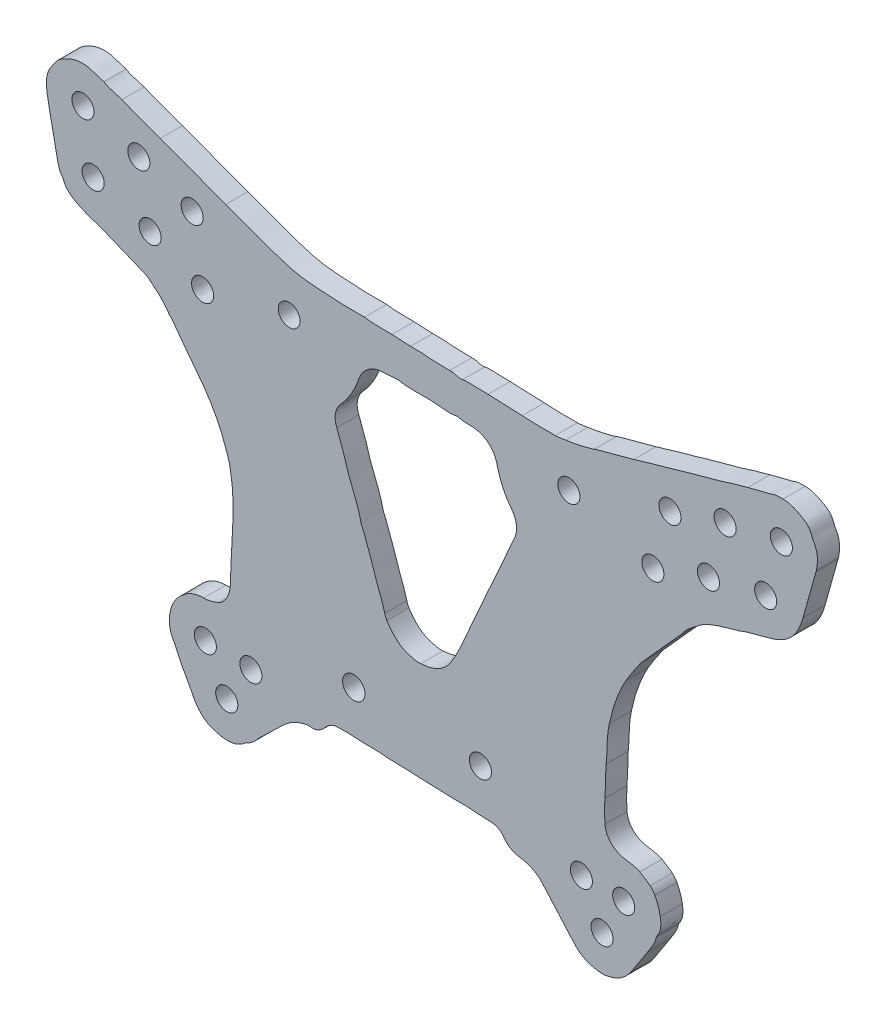
SolidWorks part; units mm, degrees
ref_plane "Front Plane" through (0, 0, 0) normal (0, 0, 1) x (1, 0, 0)
ref_plane "Top Plane" through (0, 0, 0) normal (0, 1, 0) x (1, 0, 0)
ref_plane "Right Plane" through (0, 0, 0) normal (1, 0, 0) x (0, 0, -1)
sketch "Model" plane through (0, 0, 0) normal (0, 0, 1) x (1, 0, 0)
  line L0 (141.9214, 208.6021) -> (124.7332, 209.2379) construction
  line L1 (153.9282, 246.9977) -> (115.9639, 248.6443) construction
  circle A3 centre (153.9282, 246.9977) radius 1.5
  circle A4 centre (167.6388, 251.3937) radius 1.5
  circle A5 centre (165.325, 243.566) radius 1.5
  circle A6 centre (172.8733, 246.2787) radius 1.5
  circle A7 centre (180.6355, 248.0122) radius 1.5
  circle A8 centre (175.1284, 253.7914) radius 1.5
  circle A9 centre (182.7633, 255.3651) radius 1.5
  circle A10 centre (115.9639, 248.6443) radius 1.4757
  circle A11 centre (104.2162, 245.7626) radius 1.5
  circle A12 centre (102.7959, 254.2296) radius 1.5
  circle A13 centre (95.5565, 257.0068) radius 1.5
  circle A14 centre (97.0882, 249.0091) radius 1.5
  circle A15 centre (89.3631, 251.5295) radius 1.5
  circle A16 centre (87.9744, 259.2361) radius 1.5
  circle A17 centre (141.9214, 208.6021) radius 1.5
  circle A18 centre (124.7332, 209.2379) radius 1.5237
  circle A19 centre (110.7635, 204.3383) radius 1.5
  circle A20 centre (104.5864, 204.6703) radius 1.5
  circle A21 centre (107.4953, 199.2811) radius 1.5
  circle A22 centre (155.6235, 202.6037) radius 1.5
  circle A23 centre (161.3646, 202.416) radius 1.5
  circle A24 centre (158.4323, 197.2731) radius 1.5
  spline S0 degree 2 poles (175.3982, 255.0608) (177.2596, 254.4256) (176.3428, 253.0275) knots 0 0 0 1 1 1 construction
  spline S4 degree 3 poles (104.3584, 209.5729) (103.3963, 209.582) (102.5056, 209.2728) (101.7567, 208.6986) (100.4581, 207.7028) (99.7207, 206.3826) (99.7288, 204.7593) knots 139 139 139 139 140 140 140 141 141 141 141
  spline S5 degree 3 poles (106.4003, 210.0532) (105.7457, 209.7831) (105.0841, 209.5661) (104.3584, 209.5729) knots 138 138 138 138 139 139 139 139
  spline S6 degree 3 poles (108.084, 215.6595) (108.0453, 214.815) (108.0317, 213.9694) (108.0027, 213.1244) (107.972, 212.2289) (107.7352, 211.4052) (107.177, 210.6833) (106.9637, 210.4076) (106.7223, 210.186) (106.4003, 210.0532) knots 135 135 135 135 136 136 136 137 137 137 138 138 138 138
  spline S7 degree 3 poles (108.3315, 220.639) (108.2494, 218.9791) (108.1599, 217.3196) (108.084, 215.6595) knots 134 134 134 134 135 135 135 135
  spline S8 degree 3 poles (107.9314, 226.7841) (108.3231, 224.7521) (108.4336, 222.7026) (108.3315, 220.639) knots 133 133 133 133 134 134 134 134
  spline S9 degree 3 poles (107.2797, 228.8777) (107.5183, 228.1848) (107.7919, 227.5075) (107.9314, 226.7841) knots 132 132 132 132 133 133 133 133
  spline S10 degree 3 poles (104.3046, 234.5489) (105.575, 232.807) (106.5754, 230.9228) (107.2797, 228.8777) knots 131 131 131 131 132 132 132 132
  spline S11 degree 3 poles (102.0993, 237.4386) (102.8322, 236.4737) (103.5908, 235.5276) (104.3046, 234.5489) knots 130 130 130 130 131 131 131 131
  spline S12 degree 3 poles (100.177, 240.0096) (100.3186, 239.8346) (100.446, 239.6481) (100.5808, 239.4677) (101.0864, 238.7909) (101.5883, 238.1113) (102.0993, 237.4386) knots 128 128 128 128 129 129 129 130 130 130 130
  spline S13 degree 3 poles (99.4768, 240.8565) (99.6788, 240.5533) (99.9465, 240.2945) (100.177, 240.0096) knots 127 127 127 127 128 128 128 128
  spline S14 degree 3 poles (97.03, 243.2866) (97.9346, 242.5667) (98.825, 241.8346) (99.4768, 240.8565) knots 126 126 126 126 127 127 127 127
  spline S15 degree 3 poles (96.5425, 243.6167) (96.7198, 243.5405) (96.8765, 243.4088) (97.03, 243.2866) knots 125 125 125 125 126 126 126 126
  spline S16 degree 3 poles (94.2001, 244.5874) (94.9821, 244.2667) (95.7662, 243.9506) (96.5425, 243.6167) knots 124 124 124 124 125 125 125 125
  spline S17 degree 3 poles (91.1522, 245.8331) (92.1691, 245.4201) (93.1847, 245.0039) (94.2001, 244.5874) knots 123 123 123 123 124 124 124 124
  spline S18 degree 3 poles (84.2521, 262.4934) (84.0935, 262.2961) (83.9675, 262.0728) (83.8128, 261.872) (83.2374, 261.1251) (82.9868, 260.2683) (83.0191, 259.3425) (83.0395, 258.7547) (83.117, 258.1632) (83.2293, 257.5851) (83.6537, 255.4004) (84.0984, 253.2196) (84.5458, 251.0395) (84.6532, 250.5163) (84.7614, 249.9879) (85.1442, 249.5693) (85.2359, 249.469) (85.2988, 249.3318) (85.3433, 249.2008) (85.6044, 248.4314) (86.1657, 247.9577) (86.8458, 247.5583) (87.9766, 246.8944) (89.2204, 246.5271) (90.4422, 246.097) (90.6803, 246.0132) (90.9184, 245.9281) (91.1522, 245.8331) knots 114 114 114 114 115 115 115 116 116 116 117 117 117 118 118 118 119 119 119 120 120 120 121 121 121 122 122 122 123 123 123 123
  spline S19 degree 3 poles (84.7684, 263.0465) (84.5676, 262.9012) (84.4101, 262.6898) (84.2521, 262.4934) knots 113 113 113 113 114 114 114 114
  spline S20 degree 3 poles (90.819, 263.4802) (90.7301, 263.5394) (90.6019, 263.5372) (90.4949, 263.5724) (90.2007, 263.6693) (89.9044, 263.7612) (89.6155, 263.8723) (87.8351, 264.5569) (86.245, 264.1151) (84.7684, 263.0465) knots 110 110 110 110 111 111 111 112 112 112 113 113 113 113
  spline S21 degree 3 poles (93.2681, 262.593) (92.4577, 262.9035) (91.5642, 262.984) (90.819, 263.4802) knots 109 109 109 109 110 110 110 110
  spline S22 degree 3 poles (98.4862, 260.6456) (97.5614, 260.9799) (96.627, 261.2879) (95.7055, 261.6309) (94.8871, 261.9355) (94.0837, 262.2804) (93.2681, 262.593) knots 107 107 107 107 108 108 108 109 109 109 109
  spline S23 degree 3 poles (107.3488, 257.3186) (105.1052, 258.1548) (102.8653, 259.0007) (100.624, 259.843) (99.9115, 260.1107) (99.202, 260.3869) (98.4862, 260.6456) knots 105 105 105 105 106 106 106 107 107 107 107
  spline S24 degree 3 poles (126.1998, 253.4861) (126.1173, 253.4998) (126.0308, 253.4892) (125.9462, 253.4896) (125.0168, 253.4943) (124.083, 253.4434) (123.1588, 253.5156) (121.5032, 253.6448) (119.8421, 253.6493) (118.1877, 253.8432) (116.4012, 254.0525) (114.7392, 254.6641) (113.0575, 255.2195) (111.9619, 255.5814) (110.8976, 256.0371) (109.8145, 256.4382) (108.9962, 256.7413) (108.1665, 257.0138) (107.3488, 257.3186) knots 99 99 99 99 100 100 100 101 101 101 102 102 102 103 103 103 104 104 104 105 105 105 105
  spline S25 degree 3 poles (129.9103, 253.3202) (128.673, 253.3654) (127.4302, 253.2827) (126.1998, 253.4861) knots 98 98 98 98 99 99 99 99
  spline S26 degree 3 poles (132.4427, 253.1963) (131.5983, 253.2317) (130.7548, 253.2894) (129.9103, 253.3202) knots 97 97 97 97 98 98 98 98
  spline S27 degree 3 poles (137.7603, 253.0066) (136.5498, 253.0258) (135.3367, 252.9843) (134.1333, 253.1683) (134.023, 253.1851) (133.908, 253.1716) (133.7952, 253.1733) (133.3443, 253.18) (132.893, 253.1774) (132.4427, 253.1963) knots 94 94 94 94 95 95 95 96 96 96 97 97 97 97
  spline S28 degree 3 poles (139.4981, 252.8026) (138.887, 252.659) (138.407, 253.0698) (137.8448, 253.0039) (137.8171, 253.0006) (137.7885, 253.0062) (137.7603, 253.0066) knots 92 92 92 92 93 93 93 94 94 94 94
  spline S29 degree 3 poles (142.9535, 252.807) (142.39, 252.8266) (141.8259, 252.8341) (141.2621, 252.8375) (140.672, 252.841) (140.058, 252.9341) (139.4981, 252.8026) knots 90 90 90 90 91 91 91 92 92 92 92
  spline S30 degree 3 poles (147.599, 252.6217) (146.0544, 252.7367) (144.5024, 252.7533) (142.9535, 252.807) knots 89 89 89 89 90 90 90 90
  spline S31 degree 3 poles (152.0761, 252.5182) (150.5831, 252.5305) (149.0922, 252.5105) (147.599, 252.6217) knots 88 88 88 88 89 89 89 89
  spline S32 degree 3 poles (153.4966, 252.6928) (153.0236, 252.6302) (152.5632, 252.5142) (152.0761, 252.5182) knots 87 87 87 87 88 88 88 88
  spline S33 degree 3 poles (157.3671, 253.555) (157.0445, 253.4564) (156.7226, 253.3546) (156.3966, 253.2684) (155.4422, 253.016) (154.4765, 252.8224) (153.4966, 252.6928) knots 85 85 85 85 86 86 86 87 87 87 87
  spline S34 degree 3 poles (162.7378, 255.0407) (161.0561, 254.5745) (159.3688, 254.1282) (157.6845, 253.6714) (157.5762, 253.642) (157.4747, 253.5879) (157.3671, 253.555) knots 83 83 83 83 84 84 84 85 85 85 85
  spline S35 degree 3 poles (178.2268, 259.4881) (177.4648, 259.2872) (176.689, 259.116) (175.9552, 258.8373) (175.3478, 258.6067) (174.732, 258.4454) (174.1068, 258.2847) (172.6885, 257.9201) (171.2828, 257.5071) (169.8723, 257.1125) (169.7638, 257.0821) (169.6592, 257.0384) (169.5511, 257.0068) (169.201, 256.9047) (168.8505, 256.8043) (168.4995, 256.7052) (167.4959, 256.422) (166.4904, 256.1452) (165.4887, 255.8555) (164.57, 255.5898) (163.6592, 255.2961) (162.7378, 255.0407) knots 76 76 76 76 77 77 77 78 78 78 79 79 79 80 80 80 81 81 81 82 82 82 83 83 83 83
  spline S36 degree 3 poles (182.9914, 260.519) (182.4781, 260.5212) (181.9804, 260.5454) (181.4991, 260.3351) (181.3713, 260.2792) (181.2308, 260.2504) (181.0945, 260.2158) (180.1386, 259.9731) (179.1804, 259.7394) (178.2268, 259.4881) knots 73 73 73 73 74 74 74 75 75 75 76 76 76 76
  spline S37 degree 3 poles (187.5208, 254.4157) (187.7469, 255.5503) (187.7604, 256.6541) (187.0898, 257.6746) (186.9685, 257.859) (186.9111, 258.0863) (186.8299, 258.296) (186.6293, 258.8143) (186.2912, 259.2268) (185.8204, 259.5104) (184.9484, 260.0358) (184.0645, 260.5143) (182.9914, 260.519) knots 69 69 69 69 70 70 70 71 71 71 72 72 72 73 73 73 73
  spline S38 degree 3 poles (187.4532, 254.1712) (187.476, 254.2526) (187.5043, 254.333) (187.5208, 254.4157) knots 68 68 68 68 69 69 69 69
  spline S39 degree 3 poles (185.698, 247.9046) (186.2922, 249.9909) (186.8691, 252.0821) (187.4532, 254.1712) knots 67 67 67 67 68 68 68 68
  spline S40 degree 3 poles (184.2825, 245.0495) (185.0094, 245.8818) (185.4031, 246.8688) (185.698, 247.9046) knots 66 66 66 66 67 67 67 67
  spline S41 degree 3 poles (178.0845, 242.424) (178.2136, 242.4767) (178.3578, 242.4913) (178.4937, 242.5286) (179.5521, 242.8192) (180.6132, 243.1006) (181.6667, 243.4081) (182.0167, 243.5103) (182.3561, 243.6615) (182.6841, 243.8233) (183.2958, 244.125) (183.8271, 244.5281) (184.2825, 245.0495) knots 62 62 62 62 63 63 63 64 64 64 65 65 65 66 66 66 66
  spline S42 degree 3 poles (174.3741, 241.2687) (175.6031, 241.6751) (176.8802, 241.9323) (178.0845, 242.424) knots 61 61 61 61 62 62 62 62
  spline S43 degree 3 poles (169.2822, 237.8227) (169.8117, 238.6126) (170.5471, 239.1759) (171.3015, 239.7226) (171.3472, 239.7557) (171.3947, 239.7868) (171.4372, 239.8237) (172.2894, 240.5617) (173.3359, 240.9255) (174.3741, 241.2687) knots 58 58 58 58 59 59 59 60 60 60 61 61 61 61
  spline S44 degree 3 poles (168.7158, 237.1957) (168.9032, 237.4064) (169.127, 237.5912) (169.2822, 237.8227) knots 57 57 57 57 58 58 58 58
  spline S45 degree 3 poles (164.0912, 232.0456) (165.148, 233.214) (166.2063, 234.381) (167.2602, 235.552) (167.7498, 236.096) (168.2294, 236.6488) (168.7158, 237.1957) knots 55 55 55 55 56 56 56 57 57 57 57
  spline S46 degree 3 poles (163.6955, 231.6072) (163.8044, 231.7688) (163.959, 231.8995) (164.0912, 232.0456) knots 54 54 54 54 55 55 55 55
  spline S47 degree 3 poles (161.6936, 228.5732) (162.2927, 229.6235) (163.0184, 230.602) (163.6955, 231.6072) knots 53 53 53 53 54 54 54 54
  spline S48 degree 3 poles (159.4171, 222.3231) (159.8733, 224.5233) (160.5825, 226.6253) (161.6936, 228.5732) knots 52 52 52 52 53 53 53 53
  spline S49 degree 3 poles (158.9825, 217.3704) (159.0092, 217.848) (159.0932, 218.325) (159.0858, 218.8013) (159.0675, 219.9893) (159.1745, 221.1529) (159.4171, 222.3231) knots 50 50 50 50 51 51 51 52 52 52 52
  spline S50 degree 3 poles (158.8105, 213.2372) (158.8669, 214.0246) (158.9261, 214.8069) (158.915, 215.5973) (158.9067, 216.1879) (158.9493, 216.7798) (158.9825, 217.3704) knots 48 48 48 48 49 49 49 50 50 50 50
  spline S51 degree 3 poles (158.822, 210.1979) (158.7394, 211.2055) (158.7382, 212.2288) (158.8105, 213.2372) knots 47 47 47 47 48 48 48 48
  spline S52 degree 3 poles (163.5571, 206.9674) (163.2677, 207.1281) (162.9268, 207.2091) (162.5995, 207.2856) (162.1891, 207.3816) (161.7682, 207.4323) (161.3531, 207.5093) (160.0014, 207.76) (158.9337, 208.836) (158.822, 210.1979) knots 44 44 44 44 45 45 45 46 46 46 47 47 47 47
  spline S53 degree 3 poles (164.9656, 206.0364) (164.526, 206.3854) (164.0483, 206.6945) (163.5571, 206.9674) knots 43 43 43 43 44 44 44 44
  spline S54 degree 3 poles (165.594, 205.255) (165.4379, 205.5461) (165.222, 205.8328) (164.9656, 206.0364) knots 42 42 42 42 43 43 43 43
  spline S55 degree 3 poles (166.3271, 203.102) (166.2036, 203.8558) (165.9553, 204.5815) (165.594, 205.255) knots 41 41 41 41 42 42 42 42
  spline S56 degree 3 poles (165.9276, 200.6658) (166.4643, 201.4128) (166.466, 202.2539) (166.3271, 203.102) knots 40 40 40 40 41 41 41 41
  spline S57 degree 3 poles (165.7841, 200.361) (165.8105, 200.4682) (165.863, 200.5758) (165.9276, 200.6658) knots 39 39 39 39 40 40 40 40
  spline S58 degree 3 poles (164.5379, 197.9739) (165.0235, 198.7329) (165.5632, 199.4631) (165.7841, 200.361) knots 38 38 38 38 39 39 39 39
  spline S59 degree 3 poles (162.3802, 194.6382) (162.7451, 195.1737) (163.0918, 195.7216) (163.4434, 196.2659) (163.8104, 196.8339) (164.1735, 197.4043) (164.5379, 197.9739) knots 36 36 36 36 37 37 37 38 38 38 38
  spline S60 degree 3 poles (158.9744, 192.4901) (160.4094, 192.7321) (161.5577, 193.4311) (162.3802, 194.6382) knots 35 35 35 35 36 36 36 36
  spline S61 degree 3 poles (150.3394, 199.0158) (151.5484, 197.639) (152.7682, 196.2716) (153.9733, 194.8915) (154.4743, 194.3176) (154.9591, 193.7342) (155.5909, 193.2901) (156.39, 192.7284) (158.0266, 192.3302) (158.9744, 192.4901) knots 32 32 32 32 33 33 33 34 34 34 35 35 35 35
  spline S62 degree 3 poles (146.2557, 200.8356) (146.6427, 200.6324) (147.0574, 200.584) (147.4733, 200.5088) (148.5817, 200.3084) (149.5758, 199.8853) (150.3394, 199.0158) knots 30 30 30 30 31 31 31 32 32 32 32
  spline S63 degree 3 poles (145.1581, 201.7332) (145.4365, 201.3175) (145.8241, 201.0623) (146.2557, 200.8356) knots 29 29 29 29 30 30 30 30
  spline S64 degree 3 poles (143.3091, 202.7436) (144.1079, 202.7332) (144.7214, 202.3852) (145.1581, 201.7332) knots 28 28 28 28 29 29 29 29
  spline S65 degree 3 poles (141.872, 202.8005) (142.3508, 202.7761) (142.8299, 202.7498) (143.3091, 202.7436) knots 27 27 27 27 28 28 28 28
  spline S66 degree 3 poles (140.6073, 202.8816) (141.0286, 202.8515) (141.4501, 202.8221) (141.872, 202.8005) knots 26 26 26 26 27 27 27 27
  spline S67 degree 3 poles (140.103, 202.9326) (140.2712, 202.9308) (140.4388, 202.8936) (140.6073, 202.8816) knots 25 25 25 25 26 26 26 26
  spline S68 degree 3 poles (137.4845, 202.9608) (138.3527, 202.8927) (139.2299, 202.9424) (140.103, 202.9326) knots 24 24 24 24 25 25 25 25
  spline S69 degree 3 poles (133.265, 203.1195) (134.6672, 203.0076) (136.0784, 203.0711) (137.4845, 202.9608) knots 23 23 23 23 24 24 24 24
  spline S70 degree 3 poles (129.4657, 203.2487) (130.7324, 203.2143) (131.9986, 203.2206) (133.265, 203.1195) knots 22 22 22 22 23 23 23 23
  spline S71 degree 3 poles (128.7933, 203.3149) (129.0178, 203.2969) (129.2412, 203.2548) (129.4657, 203.2487) knots 21 21 21 21 22 22 22 22
  spline S72 degree 3 poles (121.0419, 202.8048) (121.4318, 203.2024) (121.9072, 203.4531) (122.4622, 203.4764) (123.1657, 203.5058) (123.8758, 203.5332) (124.5752, 203.4719) (125.701, 203.3733) (126.8261, 203.3739) (127.9528, 203.3679) (128.2331, 203.3664) (128.5134, 203.3374) (128.7933, 203.3149) knots 17 17 17 17 18 18 18 19 19 19 20 20 20 21 21 21 21
  spline S73 degree 3 poles (120.5856, 202.3064) (120.7503, 202.4589) (120.8842, 202.6441) (121.0419, 202.8048) knots 16 16 16 16 17 17 17 17
  spline S74 degree 3 poles (118.8214, 201.6795) (119.526, 201.5553) (120.0894, 201.8469) (120.5856, 202.3064) knots 15 15 15 15 16 16 16 16
  spline S75 degree 3 poles (115.0244, 199.9023) (115.8288, 200.6708) (116.7149, 201.2932) (117.8319, 201.5453) (118.1629, 201.62) (118.474, 201.7407) (118.8214, 201.6795) knots 13 13 13 13 14 14 14 15 15 15 15
  spline S76 degree 3 poles (111.9229, 196.9174) (112.1041, 197.1303) (112.3181, 197.3161) (112.5233, 197.5076) (112.9144, 197.8725) (113.3162, 198.2261) (113.7019, 198.5965) (114.1488, 199.0255) (114.5765, 199.4744) (115.0244, 199.9023) knots 10 10 10 10 11 11 11 12 12 12 13 13 13 13
  spline S77 degree 3 poles (110.1918, 195.4717) (110.9381, 195.754) (111.4277, 196.3355) (111.9229, 196.9174) knots 9 9 9 9 10 10 10 10
  spline S78 degree 3 poles (109.9171, 195.2781) (110.0032, 195.3498) (110.0902, 195.4332) (110.1918, 195.4717) knots 8 8 8 8 9 9 9 9
  spline S79 degree 3 poles (106.3475, 194.5996) (107.647, 194.2469) (108.8526, 194.3909) (109.9171, 195.2781) knots 7 7 7 7 8 8 8 8
  spline S80 degree 3 poles (105.9465, 194.7329) (106.0834, 194.7035) (106.2117, 194.6364) (106.3475, 194.5996) knots 6 6 6 6 7 7 7 7
  spline S81 degree 3 poles (102.4253, 198.3283) (102.6668, 197.8829) (102.8621, 197.4113) (103.1194, 196.9758) (103.7721, 195.8712) (104.6332, 195.0151) (105.9465, 194.7329) knots 4 4 4 4 5 5 5 6 6 6 6
  spline S82 degree 3 poles (101.3961, 200.1737) (101.7208, 199.5491) (102.0896, 198.9474) (102.4253, 198.3283) knots 3 3 3 3 4 4 4 4
  spline S83 degree 3 poles (100.3083, 202.4566) (100.4074, 202.2881) (100.4795, 202.1038) (100.5633, 201.9264) (100.8395, 201.3414) (101.0979, 200.7473) (101.3961, 200.1737) knots 1 1 1 1 2 2 2 3 3 3 3
  spline S84 degree 3 poles (99.7288, 204.7593) (99.7058, 203.7311) (99.8274, 203.274) (100.3083, 202.4566) knots 0 0 0 0 1 1 1 1
  spline S168 degree 3 poles (100.3083, 202.4566) (99.8274, 203.274) (99.7058, 203.7311) (99.7288, 204.7593) knots 140 140 140 140 141 141 141 141
  spline S169 degree 3 poles (101.3961, 200.1737) (101.0979, 200.7473) (100.8395, 201.3414) (100.5633, 201.9264) (100.4795, 202.1038) (100.4074, 202.2881) (100.3083, 202.4566) knots 138 138 138 138 139 139 139 140 140 140 140
  spline S170 degree 3 poles (102.4253, 198.3283) (102.0896, 198.9474) (101.7208, 199.5491) (101.3961, 200.1737) knots 137 137 137 137 138 138 138 138
  spline S171 degree 3 poles (105.9465, 194.7329) (104.6332, 195.0151) (103.7721, 195.8712) (103.1194, 196.9758) (102.8621, 197.4113) (102.6668, 197.8829) (102.4253, 198.3283) knots 135 135 135 135 136 136 136 137 137 137 137
  spline S172 degree 3 poles (106.3475, 194.5996) (106.2117, 194.6364) (106.0834, 194.7035) (105.9465, 194.7329) knots 134 134 134 134 135 135 135 135
  spline S173 degree 3 poles (109.9171, 195.2781) (108.8526, 194.3909) (107.647, 194.2469) (106.3475, 194.5996) knots 133 133 133 133 134 134 134 134
  spline S174 degree 3 poles (110.1918, 195.4717) (110.0902, 195.4332) (110.0032, 195.3498) (109.9171, 195.2781) knots 132 132 132 132 133 133 133 133
  spline S175 degree 3 poles (111.9229, 196.9174) (111.4277, 196.3355) (110.9381, 195.754) (110.1918, 195.4717) knots 131 131 131 131 132 132 132 132
  spline S176 degree 3 poles (115.0244, 199.9023) (114.5765, 199.4744) (114.1488, 199.0255) (113.7019, 198.5965) (113.3162, 198.2261) (112.9144, 197.8725) (112.5233, 197.5076) (112.3181, 197.3161) (112.1041, 197.1303) (111.9229, 196.9174) knots 128 128 128 128 129 129 129 130 130 130 131 131 131 131
  spline S177 degree 3 poles (118.8214, 201.6795) (118.474, 201.7407) (118.1629, 201.62) (117.8319, 201.5453) (116.7149, 201.2932) (115.8288, 200.6708) (115.0244, 199.9023) knots 126 126 126 126 127 127 127 128 128 128 128
  spline S178 degree 3 poles (120.5856, 202.3064) (120.0894, 201.8469) (119.526, 201.5553) (118.8214, 201.6795) knots 125 125 125 125 126 126 126 126
  spline S179 degree 3 poles (121.0419, 202.8048) (120.8842, 202.6441) (120.7503, 202.4589) (120.5856, 202.3064) knots 124 124 124 124 125 125 125 125
  spline S180 degree 3 poles (128.7933, 203.3149) (128.5134, 203.3374) (128.2331, 203.3664) (127.9528, 203.3679) (126.8261, 203.3739) (125.701, 203.3733) (124.5752, 203.4719) (123.8758, 203.5332) (123.1657, 203.5058) (122.4622, 203.4764) (121.9072, 203.4531) (121.4318, 203.2024) (121.0419, 202.8048) knots 120 120 120 120 121 121 121 122 122 122 123 123 123 124 124 124 124
  spline S181 degree 3 poles (129.4657, 203.2487) (129.2412, 203.2548) (129.0178, 203.2969) (128.7933, 203.3149) knots 119 119 119 119 120 120 120 120
  spline S182 degree 3 poles (133.265, 203.1195) (131.9986, 203.2206) (130.7324, 203.2143) (129.4657, 203.2487) knots 118 118 118 118 119 119 119 119
  spline S183 degree 3 poles (137.4845, 202.9608) (136.0784, 203.0711) (134.6672, 203.0076) (133.265, 203.1195) knots 117 117 117 117 118 118 118 118
  spline S184 degree 3 poles (140.103, 202.9326) (139.2299, 202.9424) (138.3527, 202.8927) (137.4845, 202.9608) knots 116 116 116 116 117 117 117 117
  spline S185 degree 3 poles (140.6073, 202.8816) (140.4388, 202.8936) (140.2712, 202.9308) (140.103, 202.9326) knots 115 115 115 115 116 116 116 116
  spline S186 degree 3 poles (141.872, 202.8005) (141.4501, 202.8221) (141.0286, 202.8515) (140.6073, 202.8816) knots 114 114 114 114 115 115 115 115
  spline S187 degree 3 poles (143.3091, 202.7436) (142.8299, 202.7498) (142.3508, 202.7761) (141.872, 202.8005) knots 113 113 113 113 114 114 114 114
  spline S188 degree 3 poles (145.1581, 201.7332) (144.7214, 202.3852) (144.1079, 202.7332) (143.3091, 202.7436) knots 112 112 112 112 113 113 113 113
  spline S189 degree 3 poles (146.2557, 200.8356) (145.8241, 201.0623) (145.4365, 201.3175) (145.1581, 201.7332) knots 111 111 111 111 112 112 112 112
  spline S190 degree 3 poles (150.3394, 199.0158) (149.5758, 199.8853) (148.5817, 200.3084) (147.4733, 200.5088) (147.0574, 200.584) (146.6427, 200.6324) (146.2557, 200.8356) knots 109 109 109 109 110 110 110 111 111 111 111
  spline S191 degree 3 poles (158.9744, 192.4901) (158.0266, 192.3302) (156.39, 192.7284) (155.5909, 193.2901) (154.9591, 193.7342) (154.4743, 194.3176) (153.9733, 194.8915) (152.7682, 196.2716) (151.5484, 197.639) (150.3394, 199.0158) knots 106 106 106 106 107 107 107 108 108 108 109 109 109 109
  spline S192 degree 3 poles (162.3802, 194.6382) (161.5577, 193.4311) (160.4094, 192.7321) (158.9744, 192.4901) knots 105 105 105 105 106 106 106 106
  spline S193 degree 3 poles (164.5379, 197.9739) (164.1735, 197.4043) (163.8104, 196.8339) (163.4434, 196.2659) (163.0918, 195.7216) (162.7451, 195.1737) (162.3802, 194.6382) knots 103 103 103 103 104 104 104 105 105 105 105
  spline S194 degree 3 poles (165.7841, 200.361) (165.5632, 199.4631) (165.0235, 198.7329) (164.5379, 197.9739) knots 102 102 102 102 103 103 103 103
  spline S195 degree 3 poles (165.9276, 200.6658) (165.863, 200.5758) (165.8105, 200.4682) (165.7841, 200.361) knots 101 101 101 101 102 102 102 102
  spline S196 degree 3 poles (166.3271, 203.102) (166.466, 202.2539) (166.4643, 201.4128) (165.9276, 200.6658) knots 100 100 100 100 101 101 101 101
  spline S197 degree 3 poles (165.594, 205.255) (165.9553, 204.5815) (166.2036, 203.8558) (166.3271, 203.102) knots 99 99 99 99 100 100 100 100
  spline S198 degree 3 poles (164.9656, 206.0364) (165.222, 205.8328) (165.4379, 205.5461) (165.594, 205.255) knots 98 98 98 98 99 99 99 99
  spline S199 degree 3 poles (163.5571, 206.9674) (164.0483, 206.6945) (164.526, 206.3854) (164.9656, 206.0364) knots 97 97 97 97 98 98 98 98
  spline S200 degree 3 poles (158.822, 210.1979) (158.9337, 208.836) (160.0014, 207.76) (161.3531, 207.5093) (161.7682, 207.4323) (162.1891, 207.3816) (162.5995, 207.2856) (162.9268, 207.2091) (163.2677, 207.1281) (163.5571, 206.9674) knots 94 94 94 94 95 95 95 96 96 96 97 97 97 97
  spline S201 degree 3 poles (158.8105, 213.2372) (158.7382, 212.2288) (158.7394, 211.2055) (158.822, 210.1979) knots 93 93 93 93 94 94 94 94
  spline S202 degree 3 poles (158.9825, 217.3704) (158.9493, 216.7798) (158.9067, 216.1879) (158.915, 215.5973) (158.9261, 214.8069) (158.8669, 214.0246) (158.8105, 213.2372) knots 91 91 91 91 92 92 92 93 93 93 93
  spline S203 degree 3 poles (159.4171, 222.3231) (159.1745, 221.1529) (159.0675, 219.9893) (159.0858, 218.8013) (159.0932, 218.325) (159.0092, 217.848) (158.9825, 217.3704) knots 89 89 89 89 90 90 90 91 91 91 91
  spline S204 degree 3 poles (161.6936, 228.5732) (160.5825, 226.6253) (159.8733, 224.5233) (159.4171, 222.3231) knots 88 88 88 88 89 89 89 89
  spline S205 degree 3 poles (163.6955, 231.6072) (163.0184, 230.602) (162.2927, 229.6235) (161.6936, 228.5732) knots 87 87 87 87 88 88 88 88
  spline S206 degree 3 poles (164.0912, 232.0456) (163.959, 231.8995) (163.8044, 231.7688) (163.6955, 231.6072) knots 86 86 86 86 87 87 87 87
  spline S207 degree 3 poles (168.7158, 237.1957) (168.2294, 236.6488) (167.7498, 236.096) (167.2602, 235.552) (166.2063, 234.381) (165.148, 233.214) (164.0912, 232.0456) knots 84 84 84 84 85 85 85 86 86 86 86
  spline S208 degree 3 poles (169.2822, 237.8227) (169.127, 237.5912) (168.9032, 237.4064) (168.7158, 237.1957) knots 83 83 83 83 84 84 84 84
  spline S209 degree 3 poles (174.3741, 241.2687) (173.3359, 240.9255) (172.2894, 240.5617) (171.4372, 239.8237) (171.3947, 239.7868) (171.3472, 239.7557) (171.3015, 239.7226) (170.5471, 239.1759) (169.8117, 238.6126) (169.2822, 237.8227) knots 80 80 80 80 81 81 81 82 82 82 83 83 83 83
  spline S210 degree 3 poles (178.0845, 242.424) (176.8802, 241.9323) (175.6031, 241.6751) (174.3741, 241.2687) knots 79 79 79 79 80 80 80 80
  spline S211 degree 3 poles (184.2825, 245.0495) (183.8271, 244.5281) (183.2958, 244.125) (182.6841, 243.8233) (182.3561, 243.6615) (182.0167, 243.5103) (181.6667, 243.4081) (180.6132, 243.1006) (179.5521, 242.8192) (178.4937, 242.5286) (178.3578, 242.4913) (178.2136, 242.4767) (178.0845, 242.424) knots 75 75 75 75 76 76 76 77 77 77 78 78 78 79 79 79 79
  spline S212 degree 3 poles (185.698, 247.9046) (185.4031, 246.8688) (185.0094, 245.8818) (184.2825, 245.0495) knots 74 74 74 74 75 75 75 75
  spline S213 degree 3 poles (187.4532, 254.1712) (186.8691, 252.0821) (186.2922, 249.9909) (185.698, 247.9046) knots 73 73 73 73 74 74 74 74
  spline S214 degree 3 poles (187.5208, 254.4157) (187.5043, 254.333) (187.476, 254.2526) (187.4532, 254.1712) knots 72 72 72 72 73 73 73 73
  spline S215 degree 3 poles (182.9914, 260.519) (184.0645, 260.5143) (184.9484, 260.0358) (185.8204, 259.5104) (186.2912, 259.2268) (186.6293, 258.8143) (186.8299, 258.296) (186.9111, 258.0863) (186.9685, 257.859) (187.0898, 257.6746) (187.7604, 256.6541) (187.7469, 255.5503) (187.5208, 254.4157) knots 68 68 68 68 69 69 69 70 70 70 71 71 71 72 72 72 72
  spline S216 degree 3 poles (178.2268, 259.4881) (179.1804, 259.7394) (180.1386, 259.9731) (181.0945, 260.2158) (181.2308, 260.2504) (181.3713, 260.2792) (181.4991, 260.3351) (181.9804, 260.5454) (182.4781, 260.5212) (182.9914, 260.519) knots 65 65 65 65 66 66 66 67 67 67 68 68 68 68
  spline S217 degree 3 poles (162.7378, 255.0407) (163.6592, 255.2961) (164.57, 255.5898) (165.4887, 255.8555) (166.4904, 256.1452) (167.4959, 256.422) (168.4995, 256.7052) (168.8505, 256.8043) (169.201, 256.9047) (169.5511, 257.0068) (169.6592, 257.0384) (169.7638, 257.0821) (169.8723, 257.1125) (171.2828, 257.5071) (172.6885, 257.9201) (174.1068, 258.2847) (174.732, 258.4454) (175.3478, 258.6067) (175.9552, 258.8373) (176.689, 259.116) (177.4648, 259.2872) (178.2268, 259.4881) knots 58 58 58 58 59 59 59 60 60 60 61 61 61 62 62 62 63 63 63 64 64 64 65 65 65 65
  spline S218 degree 3 poles (157.3671, 253.555) (157.4747, 253.5879) (157.5762, 253.642) (157.6845, 253.6714) (159.3688, 254.1282) (161.0561, 254.5745) (162.7378, 255.0407) knots 56 56 56 56 57 57 57 58 58 58 58
  spline S219 degree 3 poles (153.4966, 252.6928) (154.4765, 252.8224) (155.4422, 253.016) (156.3966, 253.2684) (156.7226, 253.3546) (157.0445, 253.4564) (157.3671, 253.555) knots 54 54 54 54 55 55 55 56 56 56 56
  spline S220 degree 3 poles (152.0761, 252.5182) (152.5632, 252.5142) (153.0236, 252.6302) (153.4966, 252.6928) knots 53 53 53 53 54 54 54 54
  spline S221 degree 3 poles (147.599, 252.6217) (149.0922, 252.5105) (150.5831, 252.5305) (152.0761, 252.5182) knots 52 52 52 52 53 53 53 53
  spline S222 degree 3 poles (142.9535, 252.807) (144.5024, 252.7533) (146.0544, 252.7367) (147.599, 252.6217) knots 51 51 51 51 52 52 52 52
  spline S223 degree 3 poles (139.4981, 252.8026) (140.058, 252.9341) (140.672, 252.841) (141.2621, 252.8375) (141.8259, 252.8341) (142.39, 252.8266) (142.9535, 252.807) knots 49 49 49 49 50 50 50 51 51 51 51
  spline S224 degree 3 poles (137.7603, 253.0066) (137.7885, 253.0062) (137.8171, 253.0006) (137.8448, 253.0039) (138.407, 253.0698) (138.887, 252.659) (139.4981, 252.8026) knots 47 47 47 47 48 48 48 49 49 49 49
  spline S225 degree 3 poles (132.4427, 253.1963) (132.893, 253.1774) (133.3443, 253.18) (133.7952, 253.1733) (133.908, 253.1716) (134.023, 253.1851) (134.1333, 253.1683) (135.3367, 252.9843) (136.5498, 253.0258) (137.7603, 253.0066) knots 44 44 44 44 45 45 45 46 46 46 47 47 47 47
  spline S226 degree 3 poles (129.9103, 253.3202) (130.7548, 253.2894) (131.5983, 253.2317) (132.4427, 253.1963) knots 43 43 43 43 44 44 44 44
  spline S227 degree 3 poles (126.1998, 253.4861) (127.4302, 253.2827) (128.673, 253.3654) (129.9103, 253.3202) knots 42 42 42 42 43 43 43 43
  spline S228 degree 3 poles (107.3488, 257.3186) (108.1665, 257.0138) (108.9962, 256.7413) (109.8145, 256.4382) (110.8976, 256.0371) (111.9619, 255.5814) (113.0575, 255.2195) (114.7392, 254.6641) (116.4012, 254.0525) (118.1877, 253.8432) (119.8421, 253.6493) (121.5032, 253.6448) (123.1588, 253.5156) (124.083, 253.4434) (125.0168, 253.4943) (125.9462, 253.4896) (126.0308, 253.4892) (126.1173, 253.4998) (126.1998, 253.4861) knots 36 36 36 36 37 37 37 38 38 38 39 39 39 40 40 40 41 41 41 42 42 42 42
  spline S229 degree 3 poles (98.4862, 260.6456) (99.202, 260.3869) (99.9115, 260.1107) (100.624, 259.843) (102.8653, 259.0007) (105.1052, 258.1548) (107.3488, 257.3186) knots 34 34 34 34 35 35 35 36 36 36 36
  spline S230 degree 3 poles (93.2681, 262.593) (94.0837, 262.2804) (94.8871, 261.9355) (95.7055, 261.6309) (96.627, 261.2879) (97.5614, 260.9799) (98.4862, 260.6456) knots 32 32 32 32 33 33 33 34 34 34 34
  spline S231 degree 3 poles (90.819, 263.4802) (91.5642, 262.984) (92.4577, 262.9035) (93.2681, 262.593) knots 31 31 31 31 32 32 32 32
  spline S232 degree 3 poles (84.7684, 263.0465) (86.245, 264.1151) (87.8351, 264.5569) (89.6155, 263.8723) (89.9044, 263.7612) (90.2007, 263.6693) (90.4949, 263.5724) (90.6019, 263.5372) (90.7301, 263.5394) (90.819, 263.4802) knots 28 28 28 28 29 29 29 30 30 30 31 31 31 31
  spline S233 degree 3 poles (84.2521, 262.4934) (84.4101, 262.6898) (84.5676, 262.9012) (84.7684, 263.0465) knots 27 27 27 27 28 28 28 28
  spline S234 degree 3 poles (91.1522, 245.8331) (90.9184, 245.9281) (90.6803, 246.0132) (90.4422, 246.097) (89.2204, 246.5271) (87.9766, 246.8944) (86.8458, 247.5583) (86.1657, 247.9577) (85.6044, 248.4314) (85.3433, 249.2008) (85.2988, 249.3318) (85.2359, 249.469) (85.1442, 249.5693) (84.7614, 249.9879) (84.6532, 250.5163) (84.5458, 251.0395) (84.0984, 253.2196) (83.6537, 255.4004) (83.2293, 257.5851) (83.117, 258.1632) (83.0395, 258.7547) (83.0191, 259.3425) (82.9868, 260.2683) (83.2374, 261.1251) (83.8128, 261.872) (83.9675, 262.0728) (84.0935, 262.2961) (84.2521, 262.4934) knots 18 18 18 18 19 19 19 20 20 20 21 21 21 22 22 22 23 23 23 24 24 24 25 25 25 26 26 26 27 27 27 27
  spline S235 degree 3 poles (94.2001, 244.5874) (93.1847, 245.0039) (92.1691, 245.4201) (91.1522, 245.8331) knots 17 17 17 17 18 18 18 18
  spline S236 degree 3 poles (96.5425, 243.6167) (95.7662, 243.9506) (94.9821, 244.2667) (94.2001, 244.5874) knots 16 16 16 16 17 17 17 17
  spline S237 degree 3 poles (97.03, 243.2866) (96.8765, 243.4088) (96.7198, 243.5405) (96.5425, 243.6167) knots 15 15 15 15 16 16 16 16
  spline S238 degree 3 poles (99.4768, 240.8565) (98.825, 241.8346) (97.9346, 242.5667) (97.03, 243.2866) knots 14 14 14 14 15 15 15 15
  spline S239 degree 3 poles (100.177, 240.0096) (99.9465, 240.2945) (99.6788, 240.5533) (99.4768, 240.8565) knots 13 13 13 13 14 14 14 14
  spline S240 degree 3 poles (102.0993, 237.4386) (101.5883, 238.1113) (101.0864, 238.7909) (100.5808, 239.4677) (100.446, 239.6481) (100.3186, 239.8346) (100.177, 240.0096) knots 11 11 11 11 12 12 12 13 13 13 13
  spline S241 degree 3 poles (104.3046, 234.5489) (103.5908, 235.5276) (102.8322, 236.4737) (102.0993, 237.4386) knots 10 10 10 10 11 11 11 11
  spline S242 degree 3 poles (107.2797, 228.8777) (106.5754, 230.9228) (105.575, 232.807) (104.3046, 234.5489) knots 9 9 9 9 10 10 10 10
  spline S243 degree 3 poles (107.9314, 226.7841) (107.7919, 227.5075) (107.5183, 228.1848) (107.2797, 228.8777) knots 8 8 8 8 9 9 9 9
  spline S244 degree 3 poles (108.3315, 220.639) (108.4336, 222.7026) (108.3231, 224.7521) (107.9314, 226.7841) knots 7 7 7 7 8 8 8 8
  spline S245 degree 3 poles (108.084, 215.6595) (108.1599, 217.3196) (108.2494, 218.9791) (108.3315, 220.639) knots 6 6 6 6 7 7 7 7
  spline S246 degree 3 poles (106.4003, 210.0532) (106.7223, 210.186) (106.9637, 210.4076) (107.177, 210.6833) (107.7352, 211.4052) (107.972, 212.2289) (108.0027, 213.1244) (108.0317, 213.9694) (108.0453, 214.815) (108.084, 215.6595) knots 3 3 3 3 4 4 4 5 5 5 6 6 6 6
  spline S247 degree 3 poles (104.3584, 209.5729) (105.0841, 209.5661) (105.7457, 209.7831) (106.4003, 210.0532) knots 2 2 2 2 3 3 3 3
  spline S248 degree 3 poles (99.7288, 204.7593) (99.7207, 206.3826) (100.4581, 207.7028) (101.7567, 208.6986) (102.5056, 209.2728) (103.3963, 209.582) (104.3584, 209.5729) knots 0 0 0 0 1 1 1 2 2 2 2
  spline S249 degree 3 poles (129.2141, 219.3537) (129.9859, 218.1766) (130.9038, 217.1779) (132.3391, 216.7917) (132.8341, 216.6585) (133.3166, 216.5242) (133.8329, 216.5908) knots 33 33 33 33 34 34 34 35 35 35 35
  spline S250 degree 3 poles (128.9363, 220.0582) (129.0047, 219.8158) (129.0783, 219.5607) (129.2141, 219.3537) knots 32 32 32 32 33 33 33 33
  spline S251 degree 3 poles (122.4241, 238.6225) (122.4655, 238.5179) (122.4947, 238.4084) (122.5339, 238.3027) (123.0438, 236.9296) (123.5756, 235.5641) (123.9558, 234.1466) (123.9995, 233.9839) (124.0659, 233.827) (124.1264, 233.6693) (124.7114, 232.1453) (125.3905, 230.6541) (125.7292, 229.0448) (125.7464, 228.963) (125.7804, 228.8835) (125.8153, 228.8068) (126.4807, 227.3418) (126.9739, 225.8137) (127.4767, 224.289) (127.6354, 223.8078) (127.7717, 223.3165) (127.9682, 222.8508) (128.3524, 221.94) (128.6679, 221.0083) (128.9363, 220.0582) knots 24 24 24 24 25 25 25 26 26 26 27 27 27 28 28 28 29 29 29 30 30 30 31 31 31 32 32 32 32
  spline S252 degree 3 poles (127.1607, 247.8926) (126.3223, 247.4473) (125.7603, 246.7813) (125.4388, 245.8915) (125.2476, 245.3625) (125.0445, 244.8343) (124.7979, 244.3297) (124.3383, 243.3895) (123.7617, 242.5267) (123.0496, 241.7493) (122.2203, 240.844) (121.9584, 239.7998) (122.4241, 238.6225) knots 20 20 20 20 21 21 21 22 22 22 23 23 23 24 24 24 24
  spline S253 degree 3 poles (139.2186, 248.0421) (138.6327, 248.2172) (138.1021, 247.9706) (137.5475, 248.0174) (137.3789, 248.0316) (137.21, 248.0413) (137.0414, 248.0542) (136.2272, 248.1166) (135.4132, 248.2306) (134.5991, 248.2301) (133.3611, 248.2294) (132.1218, 248.1151) (130.8964, 248.3894) (130.842, 248.4015) (130.7839, 248.4049) (130.7281, 248.4016) (129.9407, 248.3551) (129.1528, 248.3155) (128.3664, 248.2554) (127.9418, 248.2229) (127.5426, 248.0954) (127.1607, 247.8926) knots 13 13 13 13 14 14 14 15 15 15 16 16 16 17 17 17 18 18 18 19 19 19 20 20 20 20
  spline S254 degree 3 poles (146.0338, 241.0777) (145.1951, 242.1332) (144.6702, 243.3401) (144.3269, 244.6338) (144.2546, 244.906) (144.1832, 245.1786) (144.1004, 245.4477) (143.5785, 247.1435) (142.0979, 247.8725) (140.8139, 247.928) (140.2794, 247.9511) (139.7173, 247.8931) (139.2186, 248.0421) knots 9 9 9 9 10 10 10 11 11 11 12 12 12 13 13 13 13
  spline S255 degree 3 poles (144.2381, 232.5007) (144.6523, 233.4261) (145.0521, 234.358) (145.4624, 235.2851) (145.8271, 236.1094) (146.1957, 236.9321) (146.5665, 237.7536) (146.756, 238.1734) (146.8264, 238.6128) (146.82, 239.0702) (146.8093, 239.8389) (146.5024, 240.4881) (146.0338, 241.0777) knots 5 5 5 5 6 6 6 7 7 7 8 8 8 9 9 9 9
  spline S256 degree 3 poles (142.9102, 229.5772) (143.3439, 230.5557) (143.801, 231.5237) (144.2381, 232.5007) knots 4 4 4 4 5 5 5 5
  spline S257 degree 3 poles (139.2511, 221.3098) (140.4893, 224.0573) (141.6892, 226.822) (142.9102, 229.5772) knots 3 3 3 3 4 4 4 4
  spline S258 degree 3 poles (137.9503, 218.847) (138.435, 219.6371) (138.8702, 220.4646) (139.2511, 221.3098) knots 2 2 2 2 3 3 3 3
  spline S259 degree 3 poles (133.8329, 216.5908) (133.9452, 216.6012) (134.0575, 216.6113) (134.1698, 216.6219) (135.7779, 216.7739) (137.0936, 217.4502) (137.9503, 218.847) knots 0 0 0 0 1 1 1 2 2 2 2
  spline S260 degree 3 poles (160.1611, 203.1591) (159.9931, 202.9562) (159.9291, 202.6673) (159.8692, 202.5335) knots 6 6 6 6 7 7 7 7 construction
  spline S261 degree 3 poles (163.0891, 202.2097) (163.215, 202.9335) (162.764, 203.6457) (162.0475, 203.7977) (161.3009, 203.956) (160.6484, 203.7478) (160.1611, 203.1591) knots 4 4 4 4 5 5 5 6 6 6 6 construction
  spline S262 degree 3 poles (159.8692, 202.5335) (159.8753, 202.074) (159.9647, 201.7814) (160.189, 201.5494) (160.5951, 201.1293) (161.0942, 200.8868) (161.6807, 200.8762) (161.8668, 200.8729) (162.0768, 200.9277) (162.2373, 201.0216) (162.691, 201.2868) (162.9961, 201.6753) (163.0891, 202.2097) knots 0 0 0 0 1 1 1 2 2 2 3 3 3 4 4 4 4 construction
  spline S263 degree 3 poles (108.9899, 199.4081) (108.9605, 200.2137) (108.3328, 200.7852) (107.4821, 200.781) knots 3 3 3 3 4 4 4 4 construction
  spline S264 degree 3 poles (105.8153, 199.2494) (105.8541, 198.318) (106.5092, 197.8508) (107.4713, 197.8286) (108.2953, 197.8096) (109.02, 198.5851) (108.9899, 199.4081) knots 1 1 1 1 2 2 2 3 3 3 3 construction
  spline S265 degree 3 poles (107.4821, 200.781) (106.5358, 200.7765) (105.7802, 200.092) (105.8153, 199.2494) knots 0 0 0 0 1 1 1 1 construction
  spline S266 degree 3 poles (111.434, 203.1318) (111.9153, 203.4253) (112.2348, 203.8347) (112.2621, 204.4037) knots 4 4 4 4 5 5 5 5 construction
  spline S267 degree 3 poles (109.0472, 204.0489) (109.3558, 203.0562) (110.5492, 202.592) (111.434, 203.1318) knots 3 3 3 3 4 4 4 4 construction
  spline S268 degree 3 poles (109.178, 205.0224) (108.9997, 204.7192) (108.9396, 204.395) (109.0472, 204.0489) knots 2 2 2 2 3 3 3 3 construction
  spline S269 degree 3 poles (111.7006, 205.5095) (110.9366, 206.0986) (109.6661, 205.8523) (109.178, 205.0224) knots 1 1 1 1 2 2 2 2 construction
  spline S270 degree 3 poles (112.2621, 204.4037) (112.2571, 204.881) (112.0529, 205.2379) (111.7006, 205.5095) knots 0 0 0 0 1 1 1 1 construction
  spline S271 degree 3 poles (125.8413, 208.2422) (126.1955, 208.5407) (126.4496, 208.903) (126.4724, 209.4653) knots 5 5 5 5 6 6 6 6 construction
  spline S272 degree 3 poles (123.3371, 209.8481) (123.2112, 209.6177) (123.206, 209.364) (123.2655, 209.1093) (123.5473, 207.9043) (124.8978, 207.4468) (125.8413, 208.2422) knots 3 3 3 3 4 4 4 5 5 5 5 construction
  spline S273 degree 3 poles (124.8476, 210.7572) (124.1805, 210.7395) (123.6614, 210.4421) (123.3371, 209.8481) knots 2 2 2 2 3 3 3 3 construction
  spline S274 degree 3 poles (126.3082, 209.9501) (126.0072, 210.5448) (125.484, 210.7742) (124.8476, 210.7572) knots 1 1 1 1 2 2 2 2 construction
  spline S275 degree 3 poles (126.4724, 209.4653) (126.4336, 209.5831) (126.3949, 209.7787) (126.3082, 209.9501) knots 0 0 0 0 1 1 1 1 construction
  spline S276 degree 3 poles (154.3409, 203.5416) (153.7799, 202.9529) (153.8375, 202.0155) (154.4908, 201.5525) (154.7129, 201.3951) (154.9865, 201.287) (155.2526, 201.2189) (156.2239, 200.9703) (157.1289, 201.7039) (157.1108, 202.7984) knots 2 2 2 2 3 3 3 4 4 4 5 5 5 5 construction
  spline S277 degree 3 poles (156.2748, 203.955) (155.6324, 204.2365) (154.829, 204.0538) (154.3409, 203.5416) knots 1 1 1 1 2 2 2 2 construction
  spline S278 degree 3 poles (157.1108, 202.7984) (157.083, 203.2891) (156.8107, 203.7201) (156.2748, 203.955) knots 0 0 0 0 1 1 1 1 construction
  spline S279 degree 3 poles (103.9885, 203.2946) (104.5538, 203.0041) (105.1852, 203.1044) (105.6992, 203.5556) (106.1708, 203.9695) (106.3478, 204.6203) (106.1333, 205.151) (105.9011, 205.7253) (105.337, 206.0728) (104.6581, 206.0601) knots 3 3 3 3 4 4 4 5 5 5 6 6 6 6 construction
  spline S280 degree 3 poles (103.5679, 203.5691) (103.6967, 203.4635) (103.8402, 203.3708) (103.9885, 203.2946) knots 2 2 2 2 3 3 3 3 construction
  spline S281 degree 3 poles (104.6581, 206.0601) (104.2223, 206.0529) (103.8319, 205.9252) (103.5087, 205.6231) (102.8768, 205.0325) (102.9008, 204.116) (103.5679, 203.5691) knots 0 0 0 0 1 1 1 2 2 2 2 construction
  spline S282 degree 3 poles (159.9131, 197.512) (159.8406, 198.2731) (159.2264, 198.7819) (158.3914, 198.7726) knots 4 4 4 4 5 5 5 5 construction
  spline S283 degree 3 poles (157.5072, 196.0599) (157.8625, 195.8297) (158.247, 195.8255) (158.6422, 195.8935) (159.4479, 196.0321) (159.9883, 196.7226) (159.9131, 197.512) knots 2 2 2 2 3 3 3 4 4 4 4 construction
  spline S284 degree 3 poles (156.8154, 197.7226) (156.6309, 197.1147) (156.9133, 196.4446) (157.5072, 196.0599) knots 1 1 1 1 2 2 2 2 construction
  spline S285 degree 3 poles (158.3914, 198.7726) (157.6784, 198.7646) (156.9931, 198.308) (156.8154, 197.7226) knots 0 0 0 0 1 1 1 1 construction
  spline S286 degree 3 poles (142.9486, 209.6952) (142.6482, 209.998) (142.2586, 210.0467) (141.8028, 210.0974) knots 6 6 6 6 7 7 7 7 construction
  spline S287 degree 3 poles (143.2246, 208.1364) (143.4759, 208.6995) (143.3579, 209.2827) (142.9486, 209.6952) knots 5 5 5 5 6 6 6 6 construction
  spline S288 degree 3 poles (142.0021, 207.2446) (142.5985, 207.2656) (142.9913, 207.6138) (143.2246, 208.1364) knots 4 4 4 4 5 5 5 5 construction
  spline S289 degree 3 poles (141.2572, 207.3532) (141.4955, 207.2811) (141.7547, 207.2358) (142.0021, 207.2446) knots 3 3 3 3 4 4 4 4 construction
  spline S290 degree 3 poles (141.2834, 210.0076) (140.6598, 209.8201) (140.2407, 209.263) (140.2278, 208.6307) (140.2159, 208.0441) (140.5977, 207.5525) (141.2572, 207.3532) knots 1 1 1 1 2 2 2 3 3 3 3 construction
  spline S291 degree 3 poles (141.8028, 210.0974) (141.6683, 210.0751) (141.4692, 210.0635) (141.2834, 210.0076) knots 0 0 0 0 1 1 1 1 construction
  spline S292 degree 3 poles (104.9195, 247.0876) (104.7352, 247.1488) (104.535, 247.1623) (104.4544, 247.1772) knots 5 5 5 5 6 6 6 6 construction
  spline S293 degree 3 poles (105.6495, 245.3204) (106.0285, 246.0364) (105.6914, 246.8313) (104.9195, 247.0876) knots 4 4 4 4 5 5 5 5 construction
  spline S294 degree 3 poles (104.4544, 247.1772) (103.8334, 247.1925) (103.4032, 247.0109) (103.0409, 246.666) (102.4579, 246.1109) (102.5006, 245.3286) (103.1511, 244.8541) (103.3303, 244.7234) (103.5389, 244.6217) (103.7481, 244.5451) (104.6347, 244.2207) (105.2648, 244.5934) (105.6495, 245.3204) knots 0 0 0 0 1 1 1 2 2 2 3 3 3 4 4 4 4 construction
  spline S295 degree 3 poles (173.4116, 244.8786) (173.5182, 244.9145) (173.6265, 244.9483) (173.7279, 244.996) (174.2749, 245.2533) (174.4891, 245.7147) (174.5134, 246.2235) knots 4 4 4 4 5 5 5 6 6 6 6 construction
  spline S296 degree 3 poles (171.4482, 245.8106) (171.9103, 244.8205) (172.5303, 244.5817) (173.4116, 244.8786) knots 3 3 3 3 4 4 4 4 construction
  spline S297 degree 3 poles (174.1661, 247.0349) (173.4485, 247.7533) (172.0404, 247.5762) (171.506, 246.6989) (171.3326, 246.4143) (171.3078, 246.1116) (171.4482, 245.8106) knots 1 1 1 1 2 2 2 3 3 3 3 construction
  spline S298 degree 3 poles (174.5134, 246.2235) (174.51, 246.5909) (174.372, 246.8288) (174.1661, 247.0349) knots 0 0 0 0 1 1 1 1 construction
  spline S299 degree 3 poles (95.4809, 248.8138) (95.64, 248.3246) (95.9884, 248.0301) (96.4478, 247.8313) (97.3497, 247.4409) (98.5439, 248.2057) (98.5656, 249.2682) knots 3 3 3 3 4 4 4 5 5 5 5 construction
  spline S300 degree 3 poles (97.9601, 250.2296) (97.1948, 250.6945) (96.1673, 250.4859) (95.6282, 249.7658) (95.4088, 249.4728) (95.3693, 249.1571) (95.4809, 248.8138) knots 1 1 1 1 2 2 2 3 3 3 3 construction
  spline S301 degree 3 poles (98.5656, 249.2682) (98.5634, 249.6564) (98.3454, 249.9956) (97.9601, 250.2296) knots 0 0 0 0 1 1 1 1 construction
  spline S302 degree 3 poles (164.6692, 242.2375) (164.8964, 242.1382) (165.1488, 242.0963) (165.2495, 242.0679) knots 5 5 5 5 6 6 6 6 construction
  spline S303 degree 3 poles (163.8271, 243.4866) (163.8316, 242.8915) (164.1321, 242.4723) (164.6692, 242.2375) knots 4 4 4 4 5 5 5 5 construction
  spline S304 degree 3 poles (165.2495, 242.0679) (166.1747, 242.0485) (166.756, 242.515) (166.8978, 243.2665) (167.0133, 243.879) (166.7477, 244.3908) (166.1721, 244.6299) (165.7129, 244.8205) (165.2385, 244.8305) (164.7707, 244.6648) (164.2249, 244.4714) (163.8234, 243.9737) (163.8271, 243.4866) knots 0 0 0 0 1 1 1 2 2 2 3 3 3 4 4 4 4 construction
  spline S305 degree 3 poles (182.1839, 248.4135) (182.0488, 248.9811) (181.4686, 249.3901) (180.7763, 249.406) knots 4 4 4 4 5 5 5 5 construction
  spline S306 degree 3 poles (181.3358, 246.9483) (181.9119, 247.232) (182.2885, 247.8827) (182.1839, 248.4135) knots 3 3 3 3 4 4 4 4 construction
  spline S307 degree 3 poles (179.2121, 247.5391) (179.6483, 246.7765) (180.5824, 246.5167) (181.3358, 246.9483) knots 2 2 2 2 3 3 3 3 construction
  spline S308 degree 3 poles (179.3529, 248.7899) (179.0364, 248.4195) (178.9846, 247.9593) (179.2121, 247.5391) knots 1 1 1 1 2 2 2 2 construction
  spline S309 degree 3 poles (180.7763, 249.406) (180.255, 249.4179) (179.675, 249.1669) (179.3529, 248.7899) knots 0 0 0 0 1 1 1 1 construction
  spline S310 degree 3 poles (181.2447, 255.0338) (181.4765, 254.4892) (182.201, 253.9993) (182.8496, 254) knots 4 4 4 4 5 5 5 5 construction
  spline S311 degree 3 poles (181.3366, 255.8319) (181.1772, 255.5819) (181.1344, 255.3173) (181.2447, 255.0338) knots 3 3 3 3 4 4 4 4 construction
  spline S312 degree 3 poles (183.755, 256.4905) (182.9471, 256.9468) (181.8098, 256.6379) (181.3366, 255.8319) knots 2 2 2 2 3 3 3 3 construction
  spline S313 degree 3 poles (184.2138, 254.983) (184.506, 255.5721) (184.3192, 256.1575) (183.755, 256.4905) knots 1 1 1 1 2 2 2 2 construction
  spline S314 degree 3 poles (182.8496, 254) (183.4528, 254.0425) (183.9326, 254.3781) (184.2138, 254.983) knots 0 0 0 0 1 1 1 1 construction
  spline S315 degree 3 poles (95.2383, 255.5409) (96.112, 255.3635) (97.0771, 256.137) (97.056, 257.0448) knots 4 4 4 4 5 5 5 5 construction
  spline S316 degree 3 poles (94.022, 257.3828) (93.7542, 256.945) (93.7885, 256.5205) (94.1456, 256.1477) (94.4446, 255.8355) (94.8156, 255.6268) (95.2383, 255.5409) knots 2 2 2 2 3 3 3 4 4 4 4 construction
  spline S317 degree 3 poles (97.056, 257.0448) (97.0233, 257.4787) (96.7654, 257.8268) (96.3329, 258.0455) (95.5561, 258.4384) (94.4756, 258.1244) (94.022, 257.3828) knots 0 0 0 0 1 1 1 2 2 2 2 construction
  spline S318 degree 3 poles (89.0354, 258.1757) (89.4011, 258.5122) (89.6694, 258.9082) (89.5165, 259.4355) (89.3707, 259.9385) (88.9902, 260.212) (88.4998, 260.342) (88.3653, 260.3776) (88.2239, 260.3872) (88.1194, 260.4035) knots 4 4 4 4 5 5 5 6 6 6 7 7 7 7 construction
  spline S319 degree 3 poles (88.1194, 260.4035) (87.4461, 260.4166) (86.9397, 260.1635) (86.5834, 259.6358) (86.3851, 259.342) (86.3325, 259.015) (86.4628, 258.6741) (86.7684, 257.8746) (87.7857, 257.4691) (88.5488, 257.8504) (88.7223, 257.9372) (88.8933, 258.045) (89.0354, 258.1757) knots 0 0 0 0 1 1 1 2 2 2 3 3 3 4 4 4 4 construction
  spline S320 degree 3 poles (114.5986, 248.0843) (114.9361, 247.5273) (115.4514, 247.2988) (116.0878, 247.3092) knots 4 4 4 4 5 5 5 5 construction
  spline S321 degree 3 poles (114.6634, 249.3417) (114.3674, 248.9452) (114.3391, 248.5125) (114.5986, 248.0843) knots 3 3 3 3 4 4 4 4 construction
  spline S322 degree 3 poles (117.4308, 248.2554) (117.6814, 248.8802) (117.5019, 249.4254) (116.9297, 249.7769) (116.1932, 250.2294) (115.1807, 250.0349) (114.6634, 249.3417) knots 1 1 1 1 2 2 2 3 3 3 3 construction
  spline S323 degree 3 poles (116.0878, 247.3092) (116.7664, 247.3189) (117.1687, 247.6022) (117.4308, 248.2554) knots 0 0 0 0 1 1 1 1 construction
  spline S324 degree 3 poles (90.6682, 250.7902) (91.292, 251.4105) (91.2076, 252.2498) (90.4614, 252.7119) (90.2092, 252.868) (89.8956, 252.925) (89.7334, 252.9831) knots 3 3 3 3 4 4 4 5 5 5 5 construction
  spline S325 degree 3 poles (89.7334, 252.9831) (88.9938, 252.9592) (88.5038, 252.7186) (88.1432, 252.2467) (87.8847, 251.9084) (87.8121, 251.5113) (88.052, 251.1469) (88.6735, 250.2029) (89.7249, 249.8522) (90.6682, 250.7902) knots 0 0 0 0 1 1 1 2 2 2 3 3 3 3 construction
  spline S326 degree 3 poles (155.4184, 247.1692) (155.4964, 247.9303) (154.9271, 248.4777) (154.0374, 248.4968) (154.0094, 248.4974) (153.9814, 248.4969) (153.8806, 248.4969) knots 4 4 4 4 5 5 5 6 6 6 6 construction
  spline S327 degree 3 poles (153.7862, 245.8616) (154.6131, 245.7256) (155.3305, 246.3132) (155.4184, 247.1692) knots 3 3 3 3 4 4 4 4 construction
  spline S328 degree 3 poles (152.8514, 248.1541) (152.1294, 247.5835) (152.1912, 246.571) (152.9941, 246.124) (153.2335, 245.9907) (153.5142, 245.9063) (153.7862, 245.8616) knots 1 1 1 1 2 2 2 3 3 3 3 construction
  spline S329 degree 3 poles (153.8806, 248.4969) (153.4941, 248.4925) (153.1399, 248.3821) (152.8514, 248.1541) knots 0 0 0 0 1 1 1 1 construction
  spline S330 degree 3 poles (102.7145, 252.7318) (103.5622, 252.656) (104.3171, 253.3808) (104.2921, 254.3364) knots 4 4 4 4 5 5 5 5 construction
  spline S331 degree 3 poles (104.2921, 254.3364) (104.2797, 254.6283) (104.098, 254.9318) (103.7799, 255.1564) (103.1027, 255.6347) (102.0003, 255.4747) (101.4777, 254.8246) (101.0691, 254.3163) (101.1079, 253.6882) (101.573, 253.2227) (101.8888, 252.9066) (102.285, 252.7702) (102.7145, 252.7318) knots 0 0 0 0 1 1 1 2 2 2 3 3 3 4 4 4 4 construction
  spline S333 degree 3 poles (173.7833, 253.1273) (174.2086, 252.5153) (174.9627, 252.2887) (175.6938, 252.5535) (176.2858, 252.7679) (176.7125, 253.4012) (176.6407, 253.9593) knots 2 2 2 2 3 3 3 4 4 4 4 construction
  spline S334 degree 3 poles (173.75, 254.383) (173.4605, 253.9671) (173.472, 253.5329) (173.7833, 253.1273) knots 1 1 1 1 2 2 2 2 construction
  spline S335 degree 3 poles (175.3982, 255.0608) (174.6408, 255.0747) (174.095, 254.8242) (173.75, 254.383) knots 0 0 0 0 1 1 1 1 construction
  spline S336 degree 3 poles (166.2054, 250.9517) (166.4864, 250.4118) (166.9509, 250.224) (167.7176, 250.252) knots 5 5 5 5 6 6 6 6 construction
  spline S337 degree 3 poles (166.5035, 252.4626) (166.0232, 252.0846) (165.9222, 251.496) (166.2054, 250.9517) knots 4 4 4 4 5 5 5 5 construction
  spline S338 degree 3 poles (168.252, 252.7626) (167.6265, 252.9577) (167.0261, 252.8739) (166.5035, 252.4626) knots 3 3 3 3 4 4 4 4 construction
  spline S339 degree 3 poles (168.1908, 250.3398) (168.7038, 250.4983) (169.1071, 251.0829) (169.1039, 251.6271) (169.1011, 252.1202) (168.7597, 252.6043) (168.252, 252.7626) knots 1 1 1 1 2 2 2 3 3 3 3 construction
  spline S340 degree 3 poles (167.7176, 250.252) (167.7528, 250.2582) (167.9794, 250.2745) (168.1908, 250.3398) knots 0 0 0 0 1 1 1 1 construction
  spline S508 degree 3 poles (137.9503, 218.847) (137.0936, 217.4502) (135.7779, 216.7739) (134.1698, 216.6219) (134.0575, 216.6113) (133.9452, 216.6012) (133.833, 216.5906) knots 33 33 33 33 34 34 34 35 35 35 35
  spline S509 degree 3 poles (139.2511, 221.3098) (138.8702, 220.4646) (138.435, 219.6371) (137.9503, 218.847) knots 32 32 32 32 33 33 33 33
  spline S510 degree 3 poles (142.9102, 229.5772) (141.6892, 226.822) (140.4893, 224.0573) (139.2511, 221.3098) knots 31 31 31 31 32 32 32 32
  spline S511 degree 3 poles (144.2381, 232.5007) (143.801, 231.5237) (143.3439, 230.5557) (142.9102, 229.5772) knots 30 30 30 30 31 31 31 31
  spline S512 degree 3 poles (146.0338, 241.0777) (146.5024, 240.4881) (146.8093, 239.8389) (146.82, 239.0702) (146.8264, 238.6128) (146.756, 238.1734) (146.5665, 237.7536) (146.1957, 236.9321) (145.8271, 236.1094) (145.4624, 235.2851) (145.0521, 234.358) (144.6523, 233.4261) (144.2381, 232.5007) knots 26 26 26 26 27 27 27 28 28 28 29 29 29 30 30 30 30
  spline S513 degree 3 poles (139.2186, 248.0421) (139.7173, 247.8931) (140.2794, 247.9511) (140.8139, 247.928) (142.0979, 247.8725) (143.5785, 247.1435) (144.1004, 245.4477) (144.1832, 245.1786) (144.2546, 244.906) (144.3269, 244.6338) (144.6702, 243.3401) (145.1951, 242.1332) (146.0338, 241.0777) knots 22 22 22 22 23 23 23 24 24 24 25 25 25 26 26 26 26
  spline S514 degree 3 poles (127.1607, 247.8926) (127.5426, 248.0954) (127.9418, 248.2229) (128.3664, 248.2554) (129.1528, 248.3155) (129.9407, 248.3551) (130.7281, 248.4016) (130.7839, 248.4049) (130.842, 248.4015) (130.8964, 248.3894) (132.1218, 248.1151) (133.3611, 248.2294) (134.5991, 248.2301) (135.4132, 248.2306) (136.2272, 248.1166) (137.0414, 248.0542) (137.21, 248.0413) (137.3789, 248.0316) (137.5475, 248.0174) (138.1021, 247.9706) (138.6327, 248.2172) (139.2186, 248.0421) knots 15 15 15 15 16 16 16 17 17 17 18 18 18 19 19 19 20 20 20 21 21 21 22 22 22 22
  spline S515 degree 3 poles (122.4241, 238.6225) (121.9584, 239.7998) (122.2203, 240.844) (123.0496, 241.7493) (123.7617, 242.5267) (124.3383, 243.3895) (124.7979, 244.3297) (125.0445, 244.8343) (125.2476, 245.3625) (125.4388, 245.8915) (125.7603, 246.7813) (126.3223, 247.4473) (127.1607, 247.8926) knots 11 11 11 11 12 12 12 13 13 13 14 14 14 15 15 15 15
  spline S516 degree 3 poles (128.9363, 220.0582) (128.6679, 221.0083) (128.3524, 221.94) (127.9682, 222.8508) (127.7717, 223.3165) (127.6354, 223.8078) (127.4767, 224.289) (126.9739, 225.8137) (126.4807, 227.3418) (125.8153, 228.8068) (125.7804, 228.8835) (125.7464, 228.963) (125.7292, 229.0448) (125.3905, 230.6541) (124.7114, 232.1453) (124.1264, 233.6693) (124.0659, 233.827) (123.9995, 233.9839) (123.9558, 234.1466) (123.5756, 235.5641) (123.0438, 236.9296) (122.5339, 238.3027) (122.4947, 238.4084) (122.4655, 238.5179) (122.4241, 238.6225) knots 3 3 3 3 4 4 4 5 5 5 6 6 6 7 7 7 8 8 8 9 9 9 10 10 10 11 11 11 11
  spline S517 degree 3 poles (129.2141, 219.3537) (129.0783, 219.5607) (129.0047, 219.8158) (128.9363, 220.0582) knots 2 2 2 2 3 3 3 3
  spline S518 degree 3 poles (133.833, 216.5906) (133.3166, 216.5242) (132.8341, 216.6585) (132.3391, 216.7917) (130.9038, 217.1779) (129.9859, 218.1766) (129.2141, 219.3537) knots 0 0 0 0 1 1 1 2 2 2 2
  spline S519 degree 3 poles (163.0891, 202.2097) (162.9961, 201.6753) (162.691, 201.2868) (162.2373, 201.0216) (162.0768, 200.9277) (161.8668, 200.8729) (161.6807, 200.8762) (161.0942, 200.8868) (160.5951, 201.1293) (160.189, 201.5494) (159.9647, 201.7814) (159.8753, 202.074) (159.8692, 202.5335) knots 3 3 3 3 4 4 4 5 5 5 6 6 6 7 7 7 7 construction
  spline S520 degree 3 poles (160.1611, 203.1591) (160.6484, 203.7478) (161.3009, 203.956) (162.0475, 203.7977) (162.764, 203.6457) (163.215, 202.9335) (163.0891, 202.2097) knots 1 1 1 1 2 2 2 3 3 3 3 construction
  spline S521 degree 3 poles (159.8692, 202.5335) (159.9291, 202.6673) (159.9931, 202.9562) (160.1611, 203.1591) knots 0 0 0 0 1 1 1 1 construction
  spline S522 degree 3 poles (105.8153, 199.2494) (105.7802, 200.092) (106.5358, 200.7765) (107.4821, 200.781) knots 3 3 3 3 4 4 4 4 construction
  spline S523 degree 3 poles (108.9899, 199.4081) (109.02, 198.5851) (108.2953, 197.8096) (107.4713, 197.8286) (106.5092, 197.8508) (105.8541, 198.318) (105.8153, 199.2494) knots 1 1 1 1 2 2 2 3 3 3 3 construction
  spline S524 degree 3 poles (107.4821, 200.781) (108.3328, 200.7852) (108.9605, 200.2137) (108.9899, 199.4081) knots 0 0 0 0 1 1 1 1 construction
  spline S525 degree 3 poles (111.7006, 205.5095) (112.0529, 205.2379) (112.2571, 204.881) (112.2621, 204.4037) knots 4 4 4 4 5 5 5 5 construction
  spline S526 degree 3 poles (109.178, 205.0224) (109.6661, 205.8523) (110.9366, 206.0986) (111.7006, 205.5095) knots 3 3 3 3 4 4 4 4 construction
  spline S527 degree 3 poles (109.0472, 204.0489) (108.9396, 204.395) (108.9997, 204.7192) (109.178, 205.0224) knots 2 2 2 2 3 3 3 3 construction
  spline S528 degree 3 poles (111.434, 203.1318) (110.5492, 202.592) (109.3558, 203.0562) (109.0472, 204.0489) knots 1 1 1 1 2 2 2 2 construction
  spline S529 degree 3 poles (112.2621, 204.4037) (112.2348, 203.8347) (111.9153, 203.4253) (111.434, 203.1318) knots 0 0 0 0 1 1 1 1 construction
  spline S530 degree 3 poles (126.3082, 209.9501) (126.3949, 209.7787) (126.4336, 209.5831) (126.4724, 209.4653) knots 5 5 5 5 6 6 6 6 construction
  spline S531 degree 3 poles (124.8476, 210.7572) (125.484, 210.7742) (126.0072, 210.5448) (126.3082, 209.9501) knots 4 4 4 4 5 5 5 5 construction
  spline S532 degree 3 poles (123.3371, 209.8481) (123.6614, 210.4421) (124.1805, 210.7395) (124.8476, 210.7572) knots 3 3 3 3 4 4 4 4 construction
  spline S533 degree 3 poles (125.8413, 208.2422) (124.8978, 207.4468) (123.5473, 207.9043) (123.2655, 209.1093) (123.206, 209.364) (123.2112, 209.6177) (123.3371, 209.8481) knots 1 1 1 1 2 2 2 3 3 3 3 construction
  spline S534 degree 3 poles (126.4724, 209.4653) (126.4496, 208.903) (126.1955, 208.5407) (125.8413, 208.2422) knots 0 0 0 0 1 1 1 1 construction
  spline S535 degree 3 poles (156.2748, 203.955) (156.8107, 203.7201) (157.083, 203.2891) (157.1108, 202.7984) knots 4 4 4 4 5 5 5 5 construction
  spline S536 degree 3 poles (154.3409, 203.5416) (154.829, 204.0538) (155.6324, 204.2365) (156.2748, 203.955) knots 3 3 3 3 4 4 4 4 construction
  spline S537 degree 3 poles (157.1108, 202.7984) (157.1289, 201.7039) (156.2239, 200.9703) (155.2526, 201.2189) (154.9865, 201.287) (154.7129, 201.3951) (154.4908, 201.5525) (153.8375, 202.0155) (153.7799, 202.9529) (154.3409, 203.5416) knots 0 0 0 0 1 1 1 2 2 2 3 3 3 3 construction
  spline S538 degree 3 poles (103.5679, 203.5691) (102.9008, 204.116) (102.8768, 205.0325) (103.5087, 205.6231) (103.8319, 205.9252) (104.2223, 206.0529) (104.6582, 206.0599) knots 4 4 4 4 5 5 5 6 6 6 6 construction
  spline S539 degree 3 poles (103.9885, 203.2946) (103.8402, 203.3708) (103.6967, 203.4635) (103.5679, 203.5691) knots 3 3 3 3 4 4 4 4 construction
  spline S540 degree 3 poles (104.6582, 206.0599) (105.337, 206.0728) (105.9011, 205.7253) (106.1333, 205.151) (106.3478, 204.6203) (106.1708, 203.9695) (105.6992, 203.5556) (105.1852, 203.1044) (104.5538, 203.0041) (103.9885, 203.2946) knots 0 0 0 0 1 1 1 2 2 2 3 3 3 3 construction
  spline S541 degree 3 poles (156.8154, 197.7226) (156.9931, 198.308) (157.6784, 198.7646) (158.3914, 198.7726) knots 4 4 4 4 5 5 5 5 construction
  spline S542 degree 3 poles (157.5072, 196.0599) (156.9133, 196.4446) (156.6309, 197.1147) (156.8154, 197.7226) knots 3 3 3 3 4 4 4 4 construction
  spline S543 degree 3 poles (159.9131, 197.512) (159.9883, 196.7226) (159.4479, 196.0321) (158.6422, 195.8935) (158.247, 195.8255) (157.8625, 195.8297) (157.5072, 196.0599) knots 1 1 1 1 2 2 2 3 3 3 3 construction
  spline S544 degree 3 poles (158.3914, 198.7726) (159.2264, 198.7819) (159.8406, 198.2731) (159.9131, 197.512) knots 0 0 0 0 1 1 1 1 construction
  spline S545 degree 3 poles (141.2834, 210.0076) (141.4692, 210.0635) (141.6683, 210.0751) (141.8028, 210.0974) knots 6 6 6 6 7 7 7 7 construction
  spline S546 degree 3 poles (141.2572, 207.3532) (140.5977, 207.5525) (140.2159, 208.0441) (140.2278, 208.6307) (140.2407, 209.263) (140.6598, 209.8201) (141.2834, 210.0076) knots 4 4 4 4 5 5 5 6 6 6 6 construction
  spline S547 degree 3 poles (142.0021, 207.2446) (141.7547, 207.2358) (141.4955, 207.2811) (141.2572, 207.3532) knots 3 3 3 3 4 4 4 4 construction
  spline S548 degree 3 poles (143.2246, 208.1364) (142.9913, 207.6138) (142.5985, 207.2656) (142.0021, 207.2446) knots 2 2 2 2 3 3 3 3 construction
  spline S549 degree 3 poles (142.9486, 209.6952) (143.3579, 209.2827) (143.4759, 208.6995) (143.2246, 208.1364) knots 1 1 1 1 2 2 2 2 construction
  spline S550 degree 3 poles (141.8028, 210.0974) (142.2586, 210.0467) (142.6482, 209.998) (142.9486, 209.6952) knots 0 0 0 0 1 1 1 1 construction
  spline S551 degree 3 poles (105.6495, 245.3204) (105.2648, 244.5934) (104.6347, 244.2207) (103.7481, 244.5451) (103.5389, 244.6217) (103.3303, 244.7234) (103.1511, 244.8541) (102.5006, 245.3286) (102.4579, 246.1109) (103.0409, 246.666) (103.4032, 247.0109) (103.8334, 247.1925) (104.4544, 247.1772) knots 2 2 2 2 3 3 3 4 4 4 5 5 5 6 6 6 6 construction
  spline S552 degree 3 poles (104.9195, 247.0876) (105.6914, 246.8313) (106.0285, 246.0364) (105.6495, 245.3204) knots 1 1 1 1 2 2 2 2 construction
  spline S553 degree 3 poles (104.4544, 247.1772) (104.535, 247.1623) (104.7352, 247.1488) (104.9195, 247.0876) knots 0 0 0 0 1 1 1 1 construction
  spline S554 degree 3 poles (174.1661, 247.0349) (174.372, 246.8288) (174.51, 246.5909) (174.5134, 246.2235) knots 5 5 5 5 6 6 6 6 construction
  spline S555 degree 3 poles (171.4482, 245.8106) (171.3078, 246.1116) (171.3326, 246.4143) (171.506, 246.6989) (172.0404, 247.5762) (173.4485, 247.7533) (174.1661, 247.0349) knots 3 3 3 3 4 4 4 5 5 5 5 construction
  spline S556 degree 3 poles (173.4116, 244.8786) (172.5303, 244.5817) (171.9103, 244.8205) (171.4482, 245.8106) knots 2 2 2 2 3 3 3 3 construction
  spline S557 degree 3 poles (174.5134, 246.2235) (174.4891, 245.7147) (174.2749, 245.2533) (173.7279, 244.996) (173.6265, 244.9483) (173.5182, 244.9145) (173.4116, 244.8786) knots 0 0 0 0 1 1 1 2 2 2 2 construction
  spline S558 degree 3 poles (97.9601, 250.2296) (98.3454, 249.9956) (98.5634, 249.6564) (98.5656, 249.2682) knots 4 4 4 4 5 5 5 5 construction
  spline S559 degree 3 poles (95.4809, 248.8138) (95.3693, 249.1571) (95.4088, 249.4728) (95.6282, 249.7658) (96.1673, 250.4859) (97.1948, 250.6945) (97.9601, 250.2296) knots 2 2 2 2 3 3 3 4 4 4 4 construction
  spline S560 degree 3 poles (98.5656, 249.2682) (98.5439, 248.2057) (97.3497, 247.4409) (96.4478, 247.8313) (95.9884, 248.0301) (95.64, 248.3246) (95.4809, 248.8138) knots 0 0 0 0 1 1 1 2 2 2 2 construction
  spline S561 degree 3 poles (163.8271, 243.4866) (163.8234, 243.9737) (164.2249, 244.4714) (164.7707, 244.6648) (165.2385, 244.8305) (165.7129, 244.8205) (166.1721, 244.6299) (166.7477, 244.3908) (167.0133, 243.879) (166.8978, 243.2665) (166.756, 242.515) (166.1747, 242.0485) (165.2495, 242.0679) knots 2 2 2 2 3 3 3 4 4 4 5 5 5 6 6 6 6 construction
  spline S562 degree 3 poles (164.6692, 242.2375) (164.1321, 242.4723) (163.8316, 242.8915) (163.8271, 243.4866) knots 1 1 1 1 2 2 2 2 construction
  spline S563 degree 3 poles (165.2495, 242.0679) (165.1488, 242.0963) (164.8964, 242.1382) (164.6692, 242.2375) knots 0 0 0 0 1 1 1 1 construction
  spline S564 degree 3 poles (179.3529, 248.7899) (179.675, 249.1669) (180.255, 249.4179) (180.7763, 249.406) knots 4 4 4 4 5 5 5 5 construction
  spline S565 degree 3 poles (179.2121, 247.5391) (178.9846, 247.9593) (179.0364, 248.4195) (179.3529, 248.7899) knots 3 3 3 3 4 4 4 4 construction
  spline S566 degree 3 poles (181.3358, 246.9483) (180.5824, 246.5167) (179.6483, 246.7765) (179.2121, 247.5391) knots 2 2 2 2 3 3 3 3 construction
  spline S567 degree 3 poles (182.1839, 248.4135) (182.2885, 247.8827) (181.9119, 247.232) (181.3358, 246.9483) knots 1 1 1 1 2 2 2 2 construction
  spline S568 degree 3 poles (180.7763, 249.406) (181.4686, 249.3901) (182.0488, 248.9811) (182.1839, 248.4135) knots 0 0 0 0 1 1 1 1 construction
  spline S569 degree 3 poles (184.2138, 254.983) (183.9326, 254.3781) (183.4528, 254.0425) (182.8496, 254) knots 4 4 4 4 5 5 5 5 construction
  spline S570 degree 3 poles (183.755, 256.4905) (184.3192, 256.1575) (184.506, 255.5721) (184.2138, 254.983) knots 3 3 3 3 4 4 4 4 construction
  spline S571 degree 3 poles (181.3366, 255.8319) (181.8098, 256.6379) (182.9471, 256.9468) (183.755, 256.4905) knots 2 2 2 2 3 3 3 3 construction
  spline S572 degree 3 poles (181.2447, 255.0338) (181.1344, 255.3173) (181.1772, 255.5819) (181.3366, 255.8319) knots 1 1 1 1 2 2 2 2 construction
  spline S573 degree 3 poles (182.8496, 254) (182.201, 253.9993) (181.4765, 254.4892) (181.2447, 255.0338) knots 0 0 0 0 1 1 1 1 construction
  spline S574 degree 3 poles (94.022, 257.3828) (94.4756, 258.1244) (95.5561, 258.4384) (96.3329, 258.0455) (96.7654, 257.8268) (97.0233, 257.4787) (97.056, 257.0448) knots 3 3 3 3 4 4 4 5 5 5 5 construction
  spline S575 degree 3 poles (95.2383, 255.5409) (94.8156, 255.6268) (94.4446, 255.8355) (94.1456, 256.1477) (93.7885, 256.5205) (93.7542, 256.945) (94.022, 257.3828) knots 1 1 1 1 2 2 2 3 3 3 3 construction
  spline S576 degree 3 poles (97.056, 257.0448) (97.0771, 256.137) (96.112, 255.3635) (95.2383, 255.5409) knots 0 0 0 0 1 1 1 1 construction
  spline S577 degree 3 poles (88.5488, 257.8504) (87.7857, 257.4691) (86.7684, 257.8746) (86.4628, 258.6741) (86.3325, 259.015) (86.3851, 259.342) (86.5834, 259.6358) (86.9397, 260.1635) (87.4461, 260.4166) (88.1194, 260.4035) knots 4 4 4 4 5 5 5 6 6 6 7 7 7 7 construction
  spline S578 degree 3 poles (88.1194, 260.4035) (88.2239, 260.3872) (88.3653, 260.3776) (88.4998, 260.342) (88.9902, 260.212) (89.3707, 259.9385) (89.5165, 259.4355) (89.6694, 258.9082) (89.4011, 258.5122) (89.0354, 258.1757) (88.8933, 258.045) (88.7223, 257.9372) (88.5488, 257.8504) knots 0 0 0 0 1 1 1 2 2 2 3 3 3 4 4 4 4 construction
  spline S579 degree 3 poles (117.4308, 248.2554) (117.1687, 247.6022) (116.7664, 247.3189) (116.0878, 247.3092) knots 4 4 4 4 5 5 5 5 construction
  spline S580 degree 3 poles (114.6634, 249.3417) (115.1807, 250.0349) (116.1932, 250.2294) (116.9297, 249.7769) (117.5019, 249.4254) (117.6814, 248.8802) (117.4308, 248.2554) knots 2 2 2 2 3 3 3 4 4 4 4 construction
  spline S581 degree 3 poles (114.5986, 248.0843) (114.3391, 248.5125) (114.3674, 248.9452) (114.6634, 249.3417) knots 1 1 1 1 2 2 2 2 construction
  spline S582 degree 3 poles (116.0878, 247.3092) (115.4514, 247.2988) (114.9361, 247.5273) (114.5986, 248.0843) knots 0 0 0 0 1 1 1 1 construction
  spline S583 degree 3 poles (88.052, 251.1469) (87.8121, 251.5113) (87.8847, 251.9084) (88.1432, 252.2467) (88.5038, 252.7186) (88.9938, 252.9592) (89.7334, 252.9831) knots 3 3 3 3 4 4 4 5 5 5 5 construction
  spline S584 degree 3 poles (89.7334, 252.9831) (89.8956, 252.925) (90.2092, 252.868) (90.4614, 252.7119) (91.2076, 252.2498) (91.292, 251.4105) (90.6682, 250.7902) (89.7249, 249.8522) (88.6735, 250.2029) (88.052, 251.1469) knots 0 0 0 0 1 1 1 2 2 2 3 3 3 3 construction
  spline S585 degree 3 poles (152.8514, 248.1541) (153.1399, 248.3821) (153.4941, 248.4925) (153.8806, 248.4969) knots 5 5 5 5 6 6 6 6 construction
  spline S586 degree 3 poles (153.7862, 245.8616) (153.5142, 245.9063) (153.2335, 245.9907) (152.9941, 246.124) (152.1912, 246.571) (152.1294, 247.5835) (152.8514, 248.1541) knots 3 3 3 3 4 4 4 5 5 5 5 construction
  spline S587 degree 3 poles (155.4184, 247.1692) (155.3305, 246.3132) (154.6131, 245.7256) (153.7862, 245.8616) knots 2 2 2 2 3 3 3 3 construction
  spline S588 degree 3 poles (153.8806, 248.4969) (153.9814, 248.4969) (154.0094, 248.4974) (154.0374, 248.4968) (154.9271, 248.4777) (155.4964, 247.9303) (155.4184, 247.1692) knots 0 0 0 0 1 1 1 2 2 2 2 construction
  spline S589 degree 3 poles (102.7145, 252.7318) (102.285, 252.7702) (101.8888, 252.9066) (101.573, 253.2227) (101.1079, 253.6882) (101.0691, 254.3163) (101.4777, 254.8246) (102.0003, 255.4747) (103.1027, 255.6347) (103.7799, 255.1564) (104.098, 254.9318) (104.2797, 254.6283) (104.2921, 254.3364) knots 1 1 1 1 2 2 2 3 3 3 4 4 4 5 5 5 5 construction
  spline S590 degree 3 poles (104.2921, 254.3364) (104.3171, 253.3808) (103.5622, 252.656) (102.7145, 252.7318) knots 0 0 0 0 1 1 1 1 construction
  spline S591 degree 3 poles (173.75, 254.383) (174.095, 254.8242) (174.6408, 255.0747) (175.3982, 255.0608) knots 5 5 5 5 6 6 6 6 construction
  spline S592 degree 3 poles (173.7833, 253.1273) (173.472, 253.5329) (173.4605, 253.9671) (173.75, 254.383) knots 4 4 4 4 5 5 5 5 construction
  spline S593 degree 3 poles (176.6407, 253.9593) (176.7125, 253.4012) (176.2858, 252.7679) (175.6938, 252.5535) (174.9627, 252.2887) (174.2086, 252.5153) (173.7833, 253.1273) knots 2 2 2 2 3 3 3 4 4 4 4 construction
  spline S595 degree 3 poles (168.1908, 250.3398) (167.9794, 250.2745) (167.7528, 250.2582) (167.7176, 250.252) knots 5 5 5 5 6 6 6 6 construction
  spline S596 degree 3 poles (168.252, 252.7626) (168.7597, 252.6043) (169.1011, 252.1202) (169.1039, 251.6271) (169.1071, 251.0829) (168.7038, 250.4983) (168.1908, 250.3398) knots 3 3 3 3 4 4 4 5 5 5 5 construction
  spline S597 degree 3 poles (166.5035, 252.4626) (167.0261, 252.8739) (167.6265, 252.9577) (168.252, 252.7626) knots 2 2 2 2 3 3 3 3 construction
  spline S598 degree 3 poles (166.2054, 250.9517) (165.9222, 251.496) (166.0232, 252.0846) (166.5035, 252.4626) knots 1 1 1 1 2 2 2 2 construction
  spline S599 degree 3 poles (167.7176, 250.252) (166.9509, 250.224) (166.4864, 250.4118) (166.2054, 250.9517) knots 0 0 0 0 1 1 1 1 construction
extrude "Boss-Extrude1" add sketch "Model" along normal blind 3 contours S4 S84 S83 S82 S81 S80 S79 S78 S77 S76 S75 S74 S73 S72 S71 S70 S69 S68 S67 S66 S65 S64 S63 S62 S61 S60 S59 S58 S57 S56 S55 S54 S53 S52 S51 S50 S49 S48 S47 S46 S45 S44 S43 S42 S41 S40 S39 S38 S37 S36 S35 region at (105.719, 208.4796, 0)
